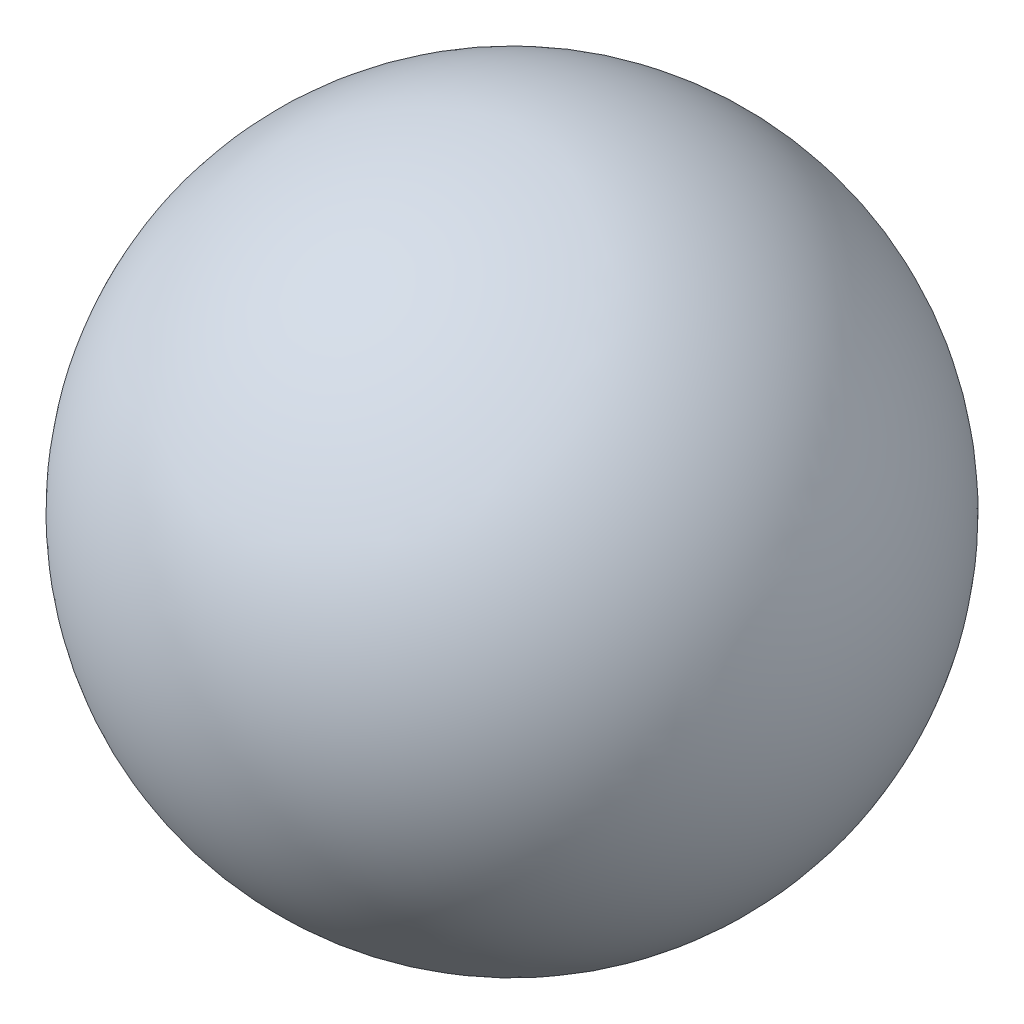
SolidWorks part; units mm, degrees
ref_plane "Front Plane" through (0, 0, 0) normal (0, 0, 1) x (1, 0, 0)
ref_plane "Top Plane" through (0, 0, 0) normal (0, 1, 0) x (1, 0, 0)
ref_plane "Right Plane" through (0, 0, 0) normal (1, 0, 0) x (0, 0, -1)
sketch "Sketch1" plane through (0, 0, 0) normal (0, 1, 0) x (1, 0, 0)
  line L0 (-1.48, 0) -> (1.48, 0) construction
  line L1 (-1.48, 0) -> (1.48, 0)
  circle A0 centre (0, 0) radius 1.48
  dimension "D1" = 2.96
revolve "Revolve1" add sketch "Sketch1" angle 360 about L1 region at (0, 0, -0.6281)
equation "\"bearing_21_OD\"= 21mm"
equation "\"pin_cirlce_diameter\"= 75mm"
equation "\"pin_diam\"= 6mm"
equation "\"gear_thickness\"= 4mm"
equation "\"ball_bearing_diam\"= 2.96mm"
equation "\"bearing_21_outer_clearance\"= 0.127mm'change this"
equation "\"bearing_15_OD\"= 15mm"
equation "\"bearing_15_outer_clearance\"= 0mm'change this"
equation "\"thrust_bearing_thickness\"= 5mm'measure this irl and change"
equation "\"D1@Sketch1\"=\"ball_bearing_diam\""
